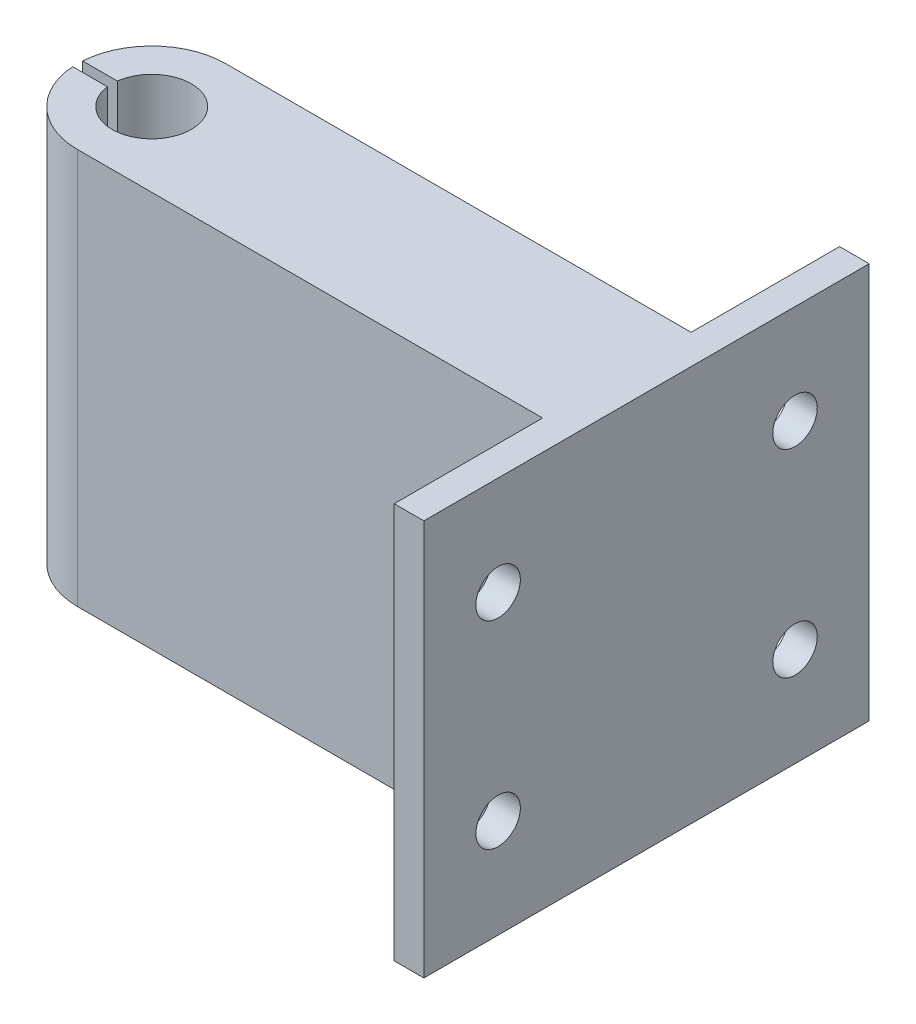
SolidWorks part; units mm, degrees
ref_plane "Front Plane" through (0, 0, 0) normal (0, 0, 1) x (1, 0, 0)
ref_plane "Top Plane" through (0, 0, 0) normal (0, 1, 0) x (1, 0, 0)
ref_plane "Right Plane" through (0, 0, 0) normal (1, 0, 0) x (0, 0, -1)
sketch "Sketch1" plane through (0, 0, 0) normal (0, 0, 1) x (1, 0, 0)
  line L0 (0, 0) -> (0, 37)
  line L1 (0, 37) -> (19, 37)
  line L2 (19, 37) -> (19, 40)
  line L3 (19, 40) -> (-57.5, 40)
  line L4 (-57.5, 40) -> (-57.5, 0)
  line L5 (-57.5, 0) -> (0, 0)
  dimension "D1" = 37
  dimension "D2" = 19
  dimension "D3" = 57.5
  dimension "D4" = 3
extrude "Boss-Extrude1" add sketch "Sketch1" along normal blind 15
sketch "Sketch2" plane through (0, 40, 0) normal (0, 1, 0) x (1, 0, 0)
  line L0 (-57.5, -7.5) -> (-50, -7.5) construction
  line L1 (-57.5, -15) -> (-57.5, 0) construction
  line L4 (-53.9686, -7) -> (-57.5, -7)
  line L5 (-57.5, -7) -> (-57.5, -8)
  line L6 (-57.5, -8) -> (-53.9686, -8)
  arc A0 (-53.9686, -8) -> (-53.9686, -7) centre (-50, -7.5) ccw
  dimension "D1" = 8
  dimension "D2" = 7.5
  dimension "D3" = 1
  dimension "D4" = 0.5
extrude "Cut-Extrude1" cut sketch "Sketch2" against normal blind 20
fillet "Fillet1" radius 7.5 2 edges at (-57.5, 20, 0) (-57.5, 20, 15)
sketch "Sketch3" plane through (0, 0, 15) normal (0, 0, 1) x (1, 0, 0)
  line L0 (19, 37) -> (0, 37)
  line L1 (0, 37) -> (0, 0)
  line L2 (0, 0) -> (-3, 0)
  line L3 (-50, 0) -> (0, 0) construction
  line L4 (-3, 0) -> (-3, 40)
  line L5 (19, 40) -> (-50, 40) construction
  line L6 (-3, 40) -> (19, 40)
  line L7 (19, 40) -> (19, 37)
  dimension "D1" = 3
extrude "Boss-Extrude2" add sketch "Sketch3" along normal blind 15
sketch "Sketch4" plane through (0, 0, 0) normal (0, 0, -1) x (-1, 0, 0)
  line L0 (-19, 40) -> (3, 40)
  line L1 (-19, 40) -> (50, 40) construction
  line L2 (3, 40) -> (3, 0)
  line L3 (50, 0) -> (0, 0) construction
  line L4 (3, 0) -> (0, 0)
  line L5 (0, 0) -> (0, 37)
  line L6 (0, 37) -> (-19, 37)
  line L7 (-19, 37) -> (-19, 40)
  dimension "D1" = 3
extrude "Boss-Extrude3" add sketch "Sketch4" along normal blind 15
sketch "Sketch5" plane through (-3, 0, 0) normal (-1, 0, 0) x (0, 0, 1)
  line L0 (-7.5, 40) -> (-7.5, 0) construction
  line L1 (-15, 40) -> (0, 40) construction
  line L2 (-15, 0) -> (0, 0) construction
  circle A0 centre (-7.5, 30) radius 2.25
  circle A1 centre (-7.5, 10) radius 2.25
  dimension "D1" = 4.5
  dimension "D2" = 4.5
  dimension "D3" = 10
  dimension "D4" = 10
extrude "Cut-Extrude2" cut sketch "Sketch5" against normal blind 15
ref_plane "Plane1" through (0, 0, 7.5) normal (0, 0, 1) x (1, 0, 0)
mirror "Mirror1" about plane through (0, 0, 7.5) normal (0, 0, 1) of "Cut-Extrude2"
sketch "Sketch6" plane through (0, 0, -15) normal (0, 0, -1) x (-1, 0, 0)
  line L1 (0, 37) -> (-26.056, 37)
  line L2 (0, 37) -> (0, 67.2435)
  line L3 (0, 67.2435) -> (-26.056, 67.2435)
  line L4 (-26.056, 37) -> (-26.056, 67.2435)
extrude "Cut-Extrude3" cut sketch "Sketch6" against normal through all both and the other way through all
